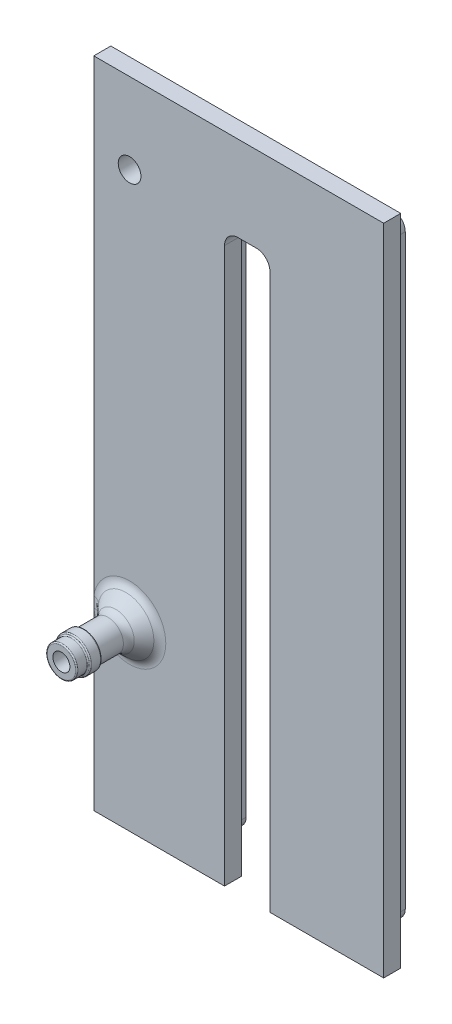
SolidWorks part; units mm, degrees
note: The reader was unsure of these and kept them because the rebuilt part matched: shared geometry of "Sketch1<3>", "Sketch5<35>", "Sketch3<52>".
ref_plane "Front Plane" through (0, 0, 0) normal (0, 0, 1) x (1, 0, 0)
ref_plane "Top Plane" through (0, 0, 0) normal (0, 1, 0) x (1, 0, 0)
ref_plane "Right Plane" through (0, 0, 0) normal (1, 0, 0) x (0, 0, -1)
sketch "Sketch1" plane through (0, 0, 0) normal (0, 0, 1) x (1, 0, 0)
  line L0 (26.9296, -20.4414) -> (26.9296, -25.4414)
  line L1 (26.9296, -58.4414) -> (26.9296, -63.4414)
  line L8 (-24.0704, -124.4414) -> (-1.0704, -124.4414)
  line L9 (-1.0704, -124.4414) -> (-1.0704, -26.8414)
  line L10 (1.3296, -24.4414) -> (4.5296, -24.4414)
  line L11 (6.9296, -26.8414) -> (6.9296, -124.4414)
  line L12 (6.9296, -124.4414) -> (26.9296, -124.4414)
  line L13 (26.9296, -124.4414) -> (26.9296, -63.4414)
  line L14 (26.9296, -9.4414) -> (-24.0704, -9.4414)
  line L15 (-24.0704, -9.4414) -> (-24.0704, -124.4414)
  line L16 (-24.0704, -124.4414) -> (-1.0704, -124.4414)
  line L17 (-1.0704, -124.4414) -> (-1.0704, -26.8414)
  line L18 (1.3296, -24.4414) -> (4.5296, -24.4414)
  line L19 (6.9296, -26.8414) -> (6.9296, -124.4414)
  line L20 (6.9296, -124.4414) -> (26.9296, -124.4414)
  line L21 (26.9296, -124.4414) -> (26.9296, -63.4414)
  line L22 (26.9296, -9.4414) -> (-24.0704, -9.4414)
  line L23 (-24.0704, -9.4414) -> (-24.0704, -124.4414)
  line L48 (-4.2704, -119.0414) -> (-4.2704, -20.2414)
  line L49 (-4.2704, -20.2414) -> (10.1296, -20.2414)
  line L50 (10.1296, -20.2414) -> (10.1296, -119.0414)
  line L51 (12.3296, -121.2414) -> (21.5296, -121.2414)
  line L52 (23.7296, -119.0414) -> (23.7296, -15.8414)
  line L53 (21.5296, -13.6414) -> (21.3296, -13.6414)
  line L54 (19.1296, -15.8414) -> (19.1296, -114.6414)
  line L55 (19.1296, -114.6414) -> (16.7296, -114.6414)
  line L56 (16.7296, -114.6414) -> (16.7296, -15.8414)
  line L57 (14.5296, -13.6414) -> (-9.6704, -13.6414)
  line L58 (-11.8704, -15.8414) -> (-11.8704, -112.6414)
  line L59 (-11.8704, -112.6414) -> (-14.2704, -112.6414)
  line L60 (-14.2704, -112.6414) -> (-14.2704, -15.8414)
  line L61 (-16.4704, -13.6414) -> (-18.6704, -13.6414)
  line L62 (-20.8704, -15.8414) -> (-20.8704, -119.0414)
  line L63 (-18.6704, -121.2414) -> (-6.4704, -121.2414)
  line L64 (-4.2704, -119.0414) -> (-4.2704, -20.2414)
  line L65 (-4.2704, -20.2414) -> (10.1296, -20.2414)
  line L66 (10.1296, -20.2414) -> (10.1296, -119.0414)
  line L67 (12.3296, -121.2414) -> (21.5296, -121.2414)
  line L68 (23.7296, -119.0414) -> (23.7296, -15.8414)
  line L69 (21.5296, -13.6414) -> (21.3296, -13.6414)
  line L70 (19.1296, -15.8414) -> (19.1296, -114.6414)
  line L71 (19.1296, -114.6414) -> (16.7296, -114.6414)
  line L72 (16.7296, -114.6414) -> (16.7296, -15.8414)
  line L73 (14.5296, -13.6414) -> (-9.6704, -13.6414)
  line L74 (-11.8704, -15.8414) -> (-11.8704, -112.6414)
  line L75 (-11.8704, -112.6414) -> (-14.2704, -112.6414)
  line L76 (-14.2704, -112.6414) -> (-14.2704, -15.8414)
  line L77 (-16.4704, -13.6414) -> (-18.6704, -13.6414)
  line L78 (-20.8704, -15.8414) -> (-20.8704, -119.0414)
  line L79 (-18.6704, -121.2414) -> (-6.4704, -121.2414)
  line L112 (26.9296, -63.4414) -> (32.9296, -60.0414)
  line L113 (26.9296, -63.4414) -> (32.9296, -60.0414)
  line L114 (32.9296, -60.0414) -> (32.9296, -56.0414)
  line L115 (32.9296, -60.0414) -> (32.9296, -56.0414)
  line L116 (32.9296, -56.0414) -> (29.9296, -56.0414)
  line L117 (32.9296, -56.0414) -> (29.9296, -56.0414)
  line L118 (29.9296, -56.0414) -> (29.9296, -58.4414)
  line L119 (29.9296, -56.0414) -> (29.9296, -58.4414)
  line L120 (29.9296, -58.4414) -> (26.9296, -58.4414)
  line L121 (29.9296, -58.4414) -> (26.9296, -58.4414)
  line L122 (26.9296, -58.4414) -> (26.9296, -25.4414)
  line L123 (26.9296, -58.4414) -> (26.9296, -25.4414)
  line L124 (26.9296, -25.4414) -> (29.9296, -25.4414)
  line L125 (26.9296, -25.4414) -> (29.9296, -25.4414)
  line L126 (29.9296, -25.4414) -> (29.9296, -27.8414)
  line L127 (29.9296, -25.4414) -> (29.9296, -27.8414)
  line L128 (29.9296, -27.8414) -> (32.9296, -27.8414)
  line L129 (29.9296, -27.8414) -> (32.9296, -27.8414)
  line L130 (32.9296, -27.8414) -> (32.9296, -23.8414)
  line L131 (32.9296, -27.8414) -> (32.9296, -23.8414)
  line L132 (32.9296, -23.8414) -> (26.9296, -20.4414)
  line L133 (32.9296, -23.8414) -> (26.9296, -20.4414)
  line L134 (26.9296, -20.4414) -> (26.9296, -9.4414)
  line L135 (26.9296, -20.4414) -> (26.9296, -9.4414)
  arc A2 (1.3296, -24.4414) -> (-1.0704, -26.8414) centre (1.3296, -26.8414) ccw
  arc A3 (6.9296, -26.8414) -> (4.5296, -24.4414) centre (4.5296, -26.8414) ccw
  arc A4 (1.3296, -24.4414) -> (-1.0704, -26.8414) centre (1.3296, -26.8414) ccw
  arc A5 (6.9296, -26.8414) -> (4.5296, -24.4414) centre (4.5296, -26.8414) ccw
  arc A24 (-6.4704, -121.2414) -> (-4.2704, -119.0414) centre (-6.4704, -119.0414) ccw
  arc A25 (10.1296, -119.0414) -> (12.3296, -121.2414) centre (12.3296, -119.0414) ccw
  arc A26 (21.5296, -121.2414) -> (23.7296, -119.0414) centre (21.5296, -119.0414) ccw
  arc A27 (23.7296, -15.8414) -> (21.5296, -13.6414) centre (21.5296, -15.8414) ccw
  arc A28 (21.3296, -13.6414) -> (19.1296, -15.8414) centre (21.3296, -15.8414) ccw
  arc A29 (16.7296, -15.8414) -> (14.5296, -13.6414) centre (14.5296, -15.8414) ccw
  arc A30 (-9.6704, -13.6414) -> (-11.8704, -15.8414) centre (-9.6704, -15.8414) ccw
  arc A31 (-14.2704, -15.8414) -> (-16.4704, -13.6414) centre (-16.4704, -15.8414) ccw
  arc A32 (-18.6704, -13.6414) -> (-20.8704, -15.8414) centre (-18.6704, -15.8414) ccw
  arc A33 (-20.8704, -119.0414) -> (-18.6704, -121.2414) centre (-18.6704, -119.0414) ccw
  arc A34 (-6.4704, -121.2414) -> (-4.2704, -119.0414) centre (-6.4704, -119.0414) ccw
  arc A35 (10.1296, -119.0414) -> (12.3296, -121.2414) centre (12.3296, -119.0414) ccw
  arc A36 (21.5296, -121.2414) -> (23.7296, -119.0414) centre (21.5296, -119.0414) ccw
  arc A37 (23.7296, -15.8414) -> (21.5296, -13.6414) centre (21.5296, -15.8414) ccw
  arc A38 (21.3296, -13.6414) -> (19.1296, -15.8414) centre (21.3296, -15.8414) ccw
  arc A39 (16.7296, -15.8414) -> (14.5296, -13.6414) centre (14.5296, -15.8414) ccw
  arc A40 (-9.6704, -13.6414) -> (-11.8704, -15.8414) centre (-9.6704, -15.8414) ccw
  arc A41 (-14.2704, -15.8414) -> (-16.4704, -13.6414) centre (-16.4704, -15.8414) ccw
  arc A42 (-18.6704, -13.6414) -> (-20.8704, -15.8414) centre (-18.6704, -15.8414) ccw
  arc A43 (-20.8704, -119.0414) -> (-18.6704, -121.2414) centre (-18.6704, -119.0414) ccw
  dimension "D1" = 0
  dimension "D2" = 0.2
extrude "Boss-Extrude1" add sketch "Sketch1" against normal blind 4 contours L78 A43 L79 A34 L64 L65 L66 A35 L67 A36 L68 A37 L69 A38 L70 L71 L72 A39 L73 A40 L74 L75 L76 A41 L77 A42
extrude "Boss-Extrude2" add sketch "Sketch1<3>" along normal blind 3 contours L78 A43 L79 A34 L64 L65 L66 A35 L67 A36 L68 A37 L69 A38 L70 L71 L72 A39 L73 A40 L74 L75 L76 A41 L77 A42 | A5 L19 L20 L21 L22 L23 L16 L17 A4 L18 A43 L78 A42 L77 A41 L76 L75 L74 A40 L73 A39 L72 L71 L70 A38 L69 A37 L68 A36 L67 A35 L66 L65 L64 A34 L79
sketch "Sketch1<3>" plane through (0, 0, 0) normal (0, 0, 1) x (1, 0, 0) same geometry as "Sketch1"
sketch "Sketch2" plane through (0, 0, -4) normal (0, 0, -1) x (-1, 0, 0)
  line L0 (14.2704, -112.6414) -> (14.2704, -15.8414) construction
  line L1 (11.8704, -112.6414) -> (14.2704, -112.6414) construction
  circle A0 centre (17.7704, -92.6414) radius 1.5
  dimension "D3" = 3
  dimension "D1" = 3.5
  dimension "D2" = 20
extrude "Cut-Extrude1" cut sketch "Sketch2" against normal through all
sketch "Sketch3" plane through (0, 0, 3) normal (0, 0, 1) x (1, 0, 0)
  circle A0 centre (-17.7704, -92.6414) radius 1.5 construction
  circle A1 centre (-17.7704, -92.6414) radius 1.5
  circle A2 centre (-17.7704, -92.6414) radius 5.5
  dimension "D1" = 4
ref_plane "Plane1" through (0, 0, 13) normal (0, 0, 1) x (1, 0, 0)
sketch "Sketch4" plane through (0, 0, 13) normal (0, 0, 1) x (1, 0, 0)
  circle A0 centre (-17.7704, -92.6414) radius 1.5 construction
  circle A1 centre (-17.7704, -92.6414) radius 1.5
  circle A2 centre (-17.7704, -92.6414) radius 3.1
  circle A3 centre (-17.7704, -92.6414) radius 2.7
  dimension "D1" = 1.6
  dimension "D2" = 0.4
ref_plane "Plane2" through (0, 0, 6) normal (0, 0, 1) x (1, 0, 0)
sketch "Sketch5" plane through (0, 0, 6) normal (0, 0, 1) x (1, 0, 0)
  circle A0 centre (-17.7704, -92.6414) radius 1.5 construction
  circle A1 centre (-17.7704, -92.6414) radius 1.5
  circle A2 centre (-17.7704, -92.6414) radius 2.7
  dimension "D1" = 1.2
loft "Loft2" add section "Sketch3" section "Sketch5"
extrude "Boss-Extrude3" add sketch "Sketch5<35>" along normal blind 9
sketch "Sketch5<35>" plane through (0, 0, 6) normal (0, 0, 1) x (1, 0, 0) same geometry as "Sketch5"
sketch "Sketch6" plane through (0, 0, -4) normal (0, 0, -1) x (-1, 0, 0)
  line L0 (14.2704, -112.6414) -> (14.2704, -15.8414) construction
  line L1 (16.4704, -13.6414) -> (18.6704, -13.6414) construction
  circle A0 centre (17.7704, -23.6414) radius 2
  dimension "D2" = 4
  dimension "D1" = 3.5
  dimension "D3" = 10
extrude "Cut-Extrude2" cut sketch "Sketch6" against normal through all
extrude "Boss-Extrude4" add sketch "Sketch4" against normal blind 2 contours A2 | A3
fillet "Fillet1" radius 2 2 edges at (-15.0704, -92.6414, 6) (-12.2704, -92.6414, 3)
fillet "Fillet2" radius 0.2 5 edges at (-14.6704, -92.6414, 13) (-14.6704, -92.6414, 11) (-15.0704, -92.6414, 15) (-15.0704, -92.6414, 13) (-15.0704, -92.6414, 11)
extrude "Cut-Extrude3" cut sketch "Sketch3<52>" along normal through all
sketch "Sketch3<52>" plane through (0, 0, 3) normal (0, 0, 1) x (1, 0, 0) same geometry as "Sketch3"
